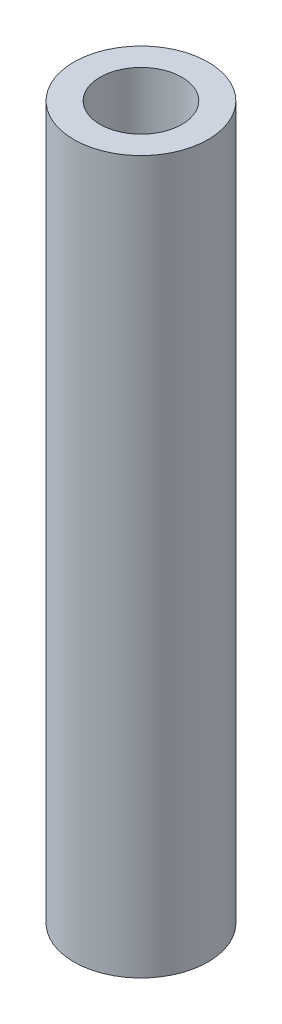
SolidWorks part; units mm, degrees
ref_plane "Front Plane" through (0, 0, 0) normal (0, 0, 1) x (1, 0, 0)
ref_plane "Top Plane" through (0, 0, 0) normal (0, 1, 0) x (1, 0, 0)
ref_plane "Right Plane" through (0, 0, 0) normal (1, 0, 0) x (0, 0, -1)
sketch "Sketch1" plane through (0, 0, 0) normal (0, 1, 0) x (1, 0, 0)
  circle A3 centre (59.4755, 35.57) radius 4.1
extrude "Boss-Extrude1" add sketch "Sketch1" against normal blind 43.5
hole_wizard "Tap Drill for M6 Tap1" positions "Sketch2" profile "Sketch3" hole size "M6" standard "ISO" end condition through all
sketch "Sketch2" plane through (0, -43.5, 0) normal (0, -1, 0) x (-1, 0, 0)
  point P0 (-59.4755, 35.57)
sketch "Sketch3" plane through (59.4755, -43.5, -35.57) normal (1, 0, 0) x (0, 0, -1)
  line L0 (0, 0) -> (0, 43.5)
  line L1 (0, 43.5) -> (2.5, 43.5)
  line L2 (2.5, 43.5) -> (2.5, 0)
  line L5 (2.5, 0) -> (0, 0)
  line L11 (0, -6.35) -> (0, 107.95) construction
  dimension "Thru Hole Dia." = 5
  dimension "Thru Hole Depth" = 43.5
